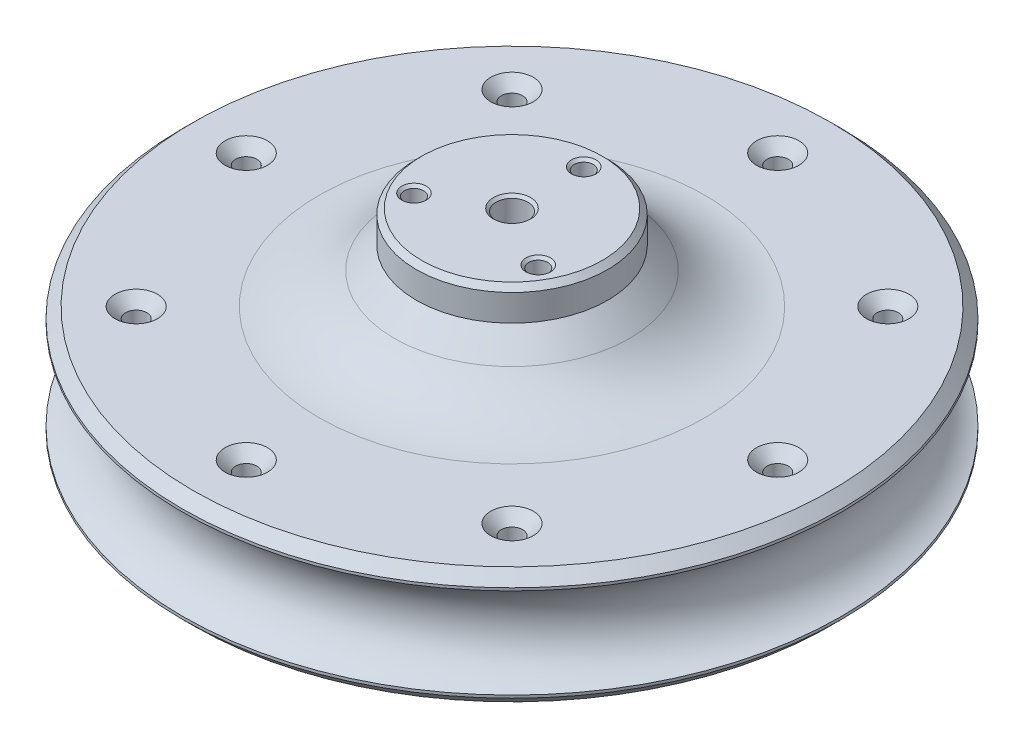
SolidWorks part; units mm, degrees
ref_plane "Спереди" through (0, 0, 0) normal (0, 0, 1) x (1, 0, 0)
ref_plane "Сверху" through (0, 0, 0) normal (0, 1, 0) x (1, 0, 0)
ref_plane "Справа" through (0, 0, 0) normal (1, 0, 0) x (0, 0, -1)
sketch "Эскиз1" plane through (0, 0, 0) normal (0, 1, 0) x (1, 0, 0)
  circle A0 centre (0, 0) radius 62
  dimension "D1" = 124
extrude "Бобышка-Вытянуть1" add sketch "Эскиз1" along normal blind 22
sketch "Эскиз3" plane through (0, 0, 0) normal (0, 0, 1) x (1, 0, 0)
  line L0 (0, 0) -> (0, 22) construction
  line L1 (62, 22) -> (-62, 22) construction
  line L2 (0, 22) -> (0, 11) construction
  line L3 (0, 11) -> (-84.2443, 11) construction
  line L9 (-56, -6.4426) -> (-56, 31.0537) construction
  circle A2 centre (-65, 11) radius 9
  dimension "D1" = 56
  dimension "D2" = 18
revolve "Вырез-Повернуть2" cut sketch "Эскиз3" angle 360 about L0
chamfer "Фаска3" distance 2 angle 45 1 edges at (0, 0, 62)
chamfer "Фаска2" distance 2 angle 45 1 edges at (0, 22, 62)
sketch "Эскиз4" plane through (0, 22, 0) normal (0, 1, 0) x (1, 0, 0)
  circle A0 centre (0, 0) radius 18
  dimension "D1" = 36
extrude "Бобышка-Вытянуть2" add sketch "Эскиз4" along normal blind 16
chamfer "Фаска4" distance 10 angle 45 1 edges at (0, 22, 18)
fillet "Скругление1" radius 20 1 edges at (0, 22, 28)
sketch "Эскиз5" plane through (0, 38, 0) normal (0, 1, 0) x (1, 0, 0)
  line L0 (0, 28.7736) -> (0, 0) construction
  line L1 (0, 0) -> (32.4148, 0) construction
  circle A0 centre (0, 0) radius 13.5 construction
  circle A1 centre (0, 13.5) radius 1.8
  circle A2 centre (11.6913, -6.75) radius 1.8
  circle A3 centre (-11.6913, -6.75) radius 1.8
  point P14 (0, 0)
  dimension "D1" = 27
  dimension "D2" = 3
  dimension "D3" = 3.6
extrude "Вырез-Вытянуть1" cut sketch "Эскиз5" against normal through all
sketch "Эскиз6" plane through (0, 0, 0) normal (0, -1, 0) x (1, 0, 0)
  circle A0 centre (0, -13.5) radius 4
  circle A1 centre (11.6913, 6.75) radius 4
  circle A2 centre (-11.6913, 6.75) radius 4
  dimension "D1" = 8
extrude "Вырез-Вытянуть2" cut sketch "Эскиз6" against normal blind 22
chamfer "Фаска5" distance 2.4 angle 45 3 edges at (0, 22, -17.5) (-11.6913, 22, 2.75) (11.6913, 22, 2.75)
chamfer "Фаска6" distance 1 angle 45 3 edges at (0, 0, -17.5) (11.6913, 0, 2.75) (-11.6913, 0, 2.75)
chamfer "Фаска7" distance 1 angle 45 1 edges at (0, 38, 18)
sketch "Эскиз7" plane through (0, 38, 0) normal (0, 1, 0) x (1, 0, 0)
  circle A0 centre (0, 0) radius 50 construction
  circle A1 centre (0, 50) radius 2
  circle A2 centre (35.3553, 35.3553) radius 2
  circle A3 centre (50, 0) radius 2
  circle A4 centre (35.3553, -35.3553) radius 2
  circle A5 centre (0, -50) radius 2
  circle A6 centre (-35.3553, -35.3553) radius 2
  circle A7 centre (-50, 0) radius 2
  circle A8 centre (-35.3553, 35.3553) radius 2
  circle A9 centre (0, 0) radius 3
  point P22 (0, 0)
  dimension "D1" = 100
  dimension "D2" = 4
  dimension "D4" = 6
  dimension "D3" = 8
extrude "Вырез-Вытянуть3" cut sketch "Эскиз7" against normal through all both and the other way through all
chamfer "Фаска8" distance 2 angle 45 8 edges at (-35.3553, 22, -33.3553) (-50, 22, 2) (-35.3553, 22, 37.3553) (0, 22, 52) (35.3553, 22, 37.3553) (50, 22, 2) (35.3553, 22, -33.3553) (0, 22, -48)
chamfer "Фаска9" distance 0.5 angle 45 4 edges at (0, 38, 3) (11.6913, 38, 8.55) (-11.6913, 38, 8.55) (0, 38, -11.7)
chamfer "Фаска10" distance 1 angle 45 9 edges at (-35.3553, 0, -33.3553) (0, 0, 3) (35.3553, 0, 37.3553) (0, 0, 52) (-35.3553, 0, 37.3553) (-50, 0, 2) (50, 0, 2) (35.3553, 0, -33.3553) (0, 0, -48)
